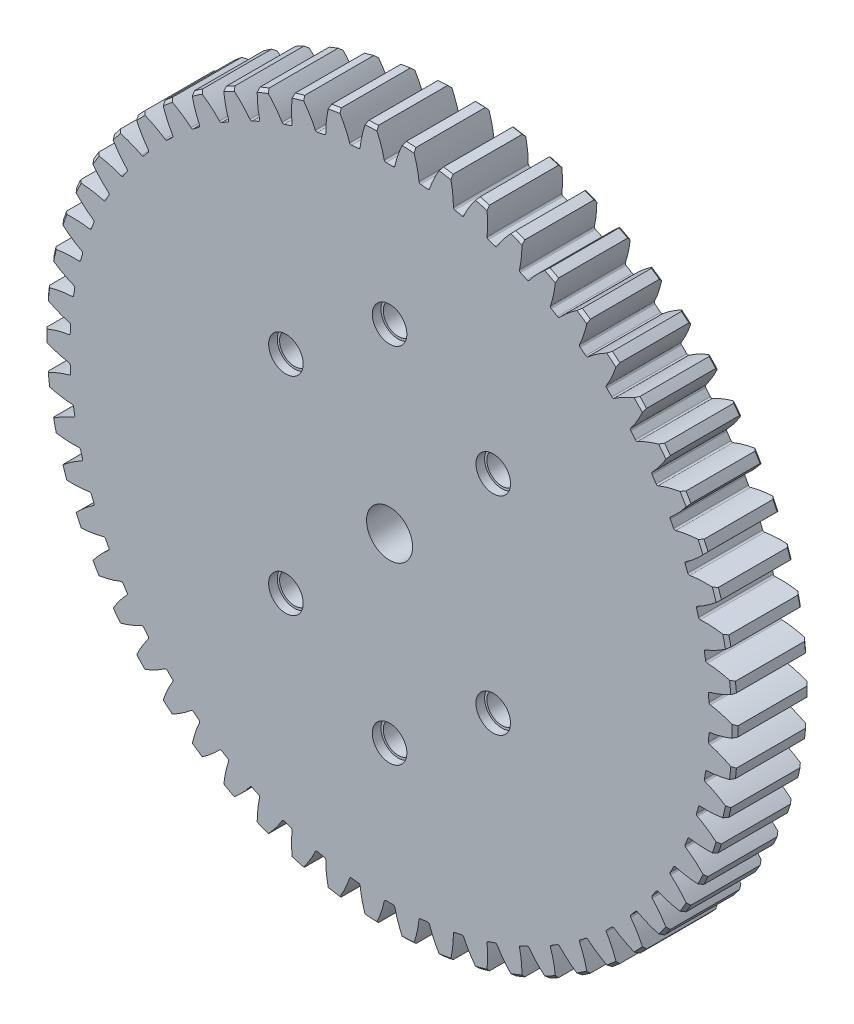
SolidWorks part; units mm, degrees
ref_plane "前视基准面" through (0, 0, 0) normal (0, 0, 1) x (1, 0, 0)
ref_plane "上视基准面" through (0, 0, 0) normal (0, 1, 0) x (1, 0, 0)
ref_plane "右视基准面" through (0, 0, 0) normal (1, 0, 0) x (0, 0, -1)
sketch "直齿轮" plane through (0, 0, 0) normal (0, 0, 1) x (1, 0, 0)
  line L0 (0, 60) -> (0, -60) construction
  line L1 (0, 0) -> (-0.7595, 54.4969)
  line L2 (0, 0) -> (0.7595, 54.4969)
  circle A0 centre (0, 0) radius 60
  arc A1 (1.5706, 57.9787) -> (-1.5706, 57.9787) centre (0, 0) ccw
  circle A2 centre (0, 0) radius 55.5
  circle A3 centre (0, 0) radius 54.5022
  spline S0 degree 4 poles (-0.9179, 54.5383) (-0.9187, 54.5901) (-0.9225, 54.6936) (-0.939, 54.9003) (-0.9775, 55.2089) (-1.0369, 55.5668) (-1.1373, 56.0545) (-1.2779, 56.6187) (-1.4659, 57.2565) (-1.7079, 57.9646) (-2.0987, 58.98) (-2.5766, 60.0423) (-3.1435, 61.1463) (-3.8445, 62.3591) (-4.4961, 63.3921) (-5.4321, 64.7538) (-7.1814, 67.0279) (-10.3067, 70.4206) (-15.1836, 74.5072) (-21.782, 78.5826) (-29.4287, 81.9501) (-37.4287, 84.3454) (-45.6452, 85.8218) (-54.3804, 86.461) (-65.2216, 86.1209) (-78.0109, 84.0601) (-92.368, 79.5208) (-105.4724, 73.0056) (-115.9344, 66.1266) (-125.7118, 58.3273) (-133.2568, 51.1228) (-140.1588, 43.3029) (-146.3909, 34.9507) (-150.9659, 27.9816) (-156.1632, 18.9498) (-160.2078, 10.4812) (-163.3054, 2.739) (-165.6424, -4.1674) (-166.8711, -8.1485) (-167.9932, -12.1608) (-169.009, -16.2015) (-169.9187, -20.267) (-170.7226, -24.3554) (-171.4212, -28.462) (-171.9405, -32.0715) (-172.3204, -35.1711) (-172.5937, -37.7633) (-172.7863, -39.8318) (-172.9532, -41.9187) (-173.094, -43.978) (-173.1994, -45.9041) (-173.275, -47.5621) (-173.3297, -49.1708) (-173.3645, -50.3566) (-173.391, -51.8199) (-173.4021, -52.6794) (-173.4112, -53.9605) (-173.4111, -55.6027) (-173.3855, -57.9403) (-173.3162, -60.4428) (-173.2066, -62.9722) (-173.0882, -65.0648) (-172.9775, -66.7453) (-172.8507, -68.4195) (-172.7079, -70.0956) (-172.5095, -72.1868) (-172.2846, -74.2765) (-172.0335, -76.3624) (-171.8117, -78.029) (-171.6956, -78.8613) (-171.6362, -79.2773) knots 0 0 0 0 0 0.000701 0.001401 0.002802 0.004203 0.005604 0.008133 0.010661 0.01319 0.015718 0.022839 0.026399 0.02996 0.034653 0.039347 0.048734 0.068727 0.096889 0.125051 0.153212 0.181374 0.209535 0.237696 0.271429 0.327752 0.384075 0.440398 0.46856 0.496721 0.553044 0.581206 0.609367 0.637529 0.66569 0.722013 0.736094 0.750174 0.764255 0.778336 0.792417 0.806497 0.820578 0.834659 0.84874 0.85578 0.86282 0.869861 0.876901 0.883942 0.890982 0.895509 0.900036 0.904564 0.909091 0.911932 0.914773 0.920455 0.931818 0.943182 0.948864 0.954545 0.960227 0.965909 0.971591 0.977273 0.988636 0.994318 1 1 1 1 1 construction
  spline S1 degree 4 poles (-0.7595, 54.4969) (-0.7603, 54.5487) (-0.764, 54.6523) (-0.7804, 54.8591) (-0.8187, 55.1679) (-0.8779, 55.526) (-0.9781, 56.0141) (-1.1185, 56.5787) (-1.3063, 57.217) (-1.548, 57.9256) (-1.9384, 58.9418) (-2.4159, 60.005) (-2.9825, 61.11) (-3.6832, 62.3238) (-4.3345, 63.3577) (-5.2702, 64.7208) (-7.0192, 66.9971) (-10.1442, 70.3935) (-15.0215, 74.4853) (-21.6211, 78.5668) (-29.2701, 81.9406) (-37.2732, 84.342) (-45.4934, 85.824) (-54.2331, 86.4687) (-65.0805, 86.1347) (-77.8781, 84.0802) (-92.2459, 79.5468) (-105.3614, 73.0356) (-115.8332, 66.1589) (-125.6206, 58.3609) (-133.174, 51.1569) (-140.0845, 43.3366) (-146.3249, 34.9834) (-150.9065, 28.0132) (-156.112, 18.9794) (-160.1638, 10.5084) (-163.2677, 2.7637) (-165.6099, -4.1452) (-166.8417, -8.1278) (-167.9668, -12.1416) (-168.9855, -16.184) (-169.8981, -20.2513) (-170.7048, -24.3414) (-171.4061, -28.45) (-171.9279, -32.0611) (-172.3099, -35.1622) (-172.5848, -37.7557) (-172.7787, -39.8252) (-172.9469, -41.9132) (-173.089, -43.9735) (-173.1956, -45.9007) (-173.2722, -47.5596) (-173.3278, -49.1691) (-173.3618, -50.3044) (-173.3834, -51.428) (-173.3926, -52.0027) (-173.396, -52.2556) knots 0 0 0 0 0 0.000701 0.001401 0.002802 0.004203 0.005604 0.008133 0.010661 0.01319 0.015718 0.022839 0.026399 0.02996 0.034653 0.039347 0.048734 0.068727 0.096889 0.125051 0.153212 0.181374 0.209535 0.237696 0.271429 0.327752 0.384075 0.440398 0.46856 0.496721 0.553044 0.581206 0.609367 0.637529 0.66569 0.722013 0.736094 0.750174 0.764255 0.778336 0.792417 0.806497 0.820578 0.834659 0.84874 0.85578 0.86282 0.869861 0.876901 0.883942 0.890982 0.895509 0.900036 0.904564 0.908309 0.908309 0.908309 0.908309 0.908309
  spline S2 degree 4 poles (0.9179, 54.5383) (0.9187, 54.5901) (0.9225, 54.6936) (0.939, 54.9003) (0.9775, 55.2089) (1.0369, 55.5668) (1.1373, 56.0545) (1.2779, 56.6187) (1.4659, 57.2565) (1.7079, 57.9646) (2.0987, 58.98) (2.5766, 60.0423) (3.1435, 61.1463) (3.8445, 62.3591) (4.4961, 63.3921) (5.4321, 64.7538) (7.1814, 67.0279) (10.3067, 70.4206) (15.1836, 74.5072) (21.782, 78.5826) (29.4287, 81.9501) (37.4287, 84.3454) (45.6452, 85.8218) (54.3804, 86.461) (65.2216, 86.1209) (78.0109, 84.0601) (92.368, 79.5208) (105.4724, 73.0056) (115.9344, 66.1266) (125.7118, 58.3273) (133.2568, 51.1228) (140.1588, 43.3029) (146.3909, 34.9507) (150.9659, 27.9816) (156.1632, 18.9498) (160.2078, 10.4812) (163.3054, 2.739) (165.6424, -4.1674) (166.8711, -8.1485) (167.9932, -12.1608) (169.009, -16.2015) (169.9187, -20.267) (170.7226, -24.3554) (171.4212, -28.462) (171.9405, -32.0715) (172.3204, -35.1711) (172.5937, -37.7633) (172.7863, -39.8318) (172.9532, -41.9187) (173.094, -43.978) (173.1994, -45.9041) (173.275, -47.5621) (173.3297, -49.1708) (173.3645, -50.3566) (173.391, -51.8199) (173.4021, -52.6794) (173.4112, -53.9605) (173.4111, -55.6027) (173.3855, -57.9403) (173.3162, -60.4428) (173.2066, -62.9722) (173.0882, -65.0648) (172.9775, -66.7453) (172.8507, -68.4195) (172.7079, -70.0956) (172.5095, -72.1868) (172.2846, -74.2765) (172.0335, -76.3624) (171.8117, -78.029) (171.6956, -78.8613) (171.6362, -79.2773) knots 0 0 0 0 0 0.000701 0.001401 0.002802 0.004203 0.005604 0.008133 0.010661 0.01319 0.015718 0.022839 0.026399 0.02996 0.034653 0.039347 0.048734 0.068727 0.096889 0.125051 0.153212 0.181374 0.209535 0.237696 0.271429 0.327752 0.384075 0.440398 0.46856 0.496721 0.553044 0.581206 0.609367 0.637529 0.66569 0.722013 0.736094 0.750174 0.764255 0.778336 0.792417 0.806497 0.820578 0.834659 0.84874 0.85578 0.86282 0.869861 0.876901 0.883942 0.890982 0.895509 0.900036 0.904564 0.909091 0.911932 0.914773 0.920455 0.931818 0.943182 0.948864 0.954545 0.960227 0.965909 0.971591 0.977273 0.988636 0.994318 1 1 1 1 1 construction
  spline S3 degree 4 poles (0.7595, 54.4969) (0.7603, 54.5487) (0.764, 54.6523) (0.7804, 54.8591) (0.8187, 55.1679) (0.8779, 55.526) (0.9781, 56.0141) (1.1185, 56.5787) (1.3063, 57.217) (1.548, 57.9256) (1.9384, 58.9418) (2.4159, 60.005) (2.9825, 61.11) (3.6832, 62.3238) (4.3345, 63.3577) (5.2702, 64.7208) (7.0192, 66.9971) (10.1442, 70.3935) (15.0215, 74.4853) (21.6211, 78.5668) (29.2701, 81.9406) (37.2732, 84.342) (45.4934, 85.824) (54.2331, 86.4687) (65.0805, 86.1347) (77.8781, 84.0802) (92.2459, 79.5468) (105.3614, 73.0356) (115.8332, 66.1589) (125.6206, 58.3609) (133.174, 51.1569) (140.0845, 43.3366) (146.3249, 34.9834) (150.9065, 28.0132) (156.112, 18.9794) (160.1638, 10.5084) (163.2677, 2.7637) (165.6099, -4.1452) (166.8417, -8.1278) (167.9668, -12.1416) (168.9855, -16.184) (169.8981, -20.2513) (170.7048, -24.3414) (171.4061, -28.45) (171.9279, -32.0611) (172.3099, -35.1622) (172.5848, -37.7557) (172.7787, -39.8252) (172.9469, -41.9132) (173.089, -43.9735) (173.1956, -45.9007) (173.2722, -47.5596) (173.3278, -49.1691) (173.3618, -50.3044) (173.3834, -51.428) (173.3926, -52.0027) (173.396, -52.2556) knots 0 0 0 0 0 0.000701 0.001401 0.002802 0.004203 0.005604 0.008133 0.010661 0.01319 0.015718 0.022839 0.026399 0.02996 0.034653 0.039347 0.048734 0.068727 0.096889 0.125051 0.153212 0.181374 0.209535 0.237696 0.271429 0.327752 0.384075 0.440398 0.46856 0.496721 0.553044 0.581206 0.609367 0.637529 0.66569 0.722013 0.736094 0.750174 0.764255 0.778336 0.792417 0.806497 0.820578 0.834659 0.84874 0.85578 0.86282 0.869861 0.876901 0.883942 0.890982 0.895509 0.900036 0.904564 0.908309 0.908309 0.908309 0.908309 0.908309
  dimension "齿顶圆" = 120
  dimension "分度圆" = 116
  dimension "齿根圆" = 111
  dimension "基圆直径" = 109.0043
  dimension "D1" = 3.1416
extrude "齿轮毛坯" add sketch "直齿轮" along normal mid plane 13 contours A0
chamfer "轮齿倒角" distance 0.5 angle 45 2 edges at (60, 0, -6.5) (60, 0, 6.5)
sketch "草图2" plane through (0, 0, 0) normal (0, 0, 1) x (1, 0, 0)
  line L0 (0, 0) -> (-0.7595, 54.4969) construction
  line L1 (0, 0) -> (0.7595, 54.4969) construction
  line L2 (0, 0) -> (-0.7595, 54.4969)
  line L3 (0, 0) -> (0.7595, 54.4969)
  circle A0 centre (0, 0) radius 60 construction
  circle A1 centre (0, 0) radius 60
  circle A2 centre (0, 0) radius 55.5 construction
  circle A3 centre (0, 0) radius 55.5
  spline S0 degree 4 poles (998.4423, 32.7635) (-28.6861, 47.8423) (-1.4617, 50.0963) (-0.5059, 52.6455) (-0.8187, 55.1679) (-0.8779, 55.526) (-0.9781, 56.0141) (-1.1185, 56.5787) (-1.3063, 57.217) (-1.548, 57.9256) (-1.9384, 58.9418) (-2.4159, 60.005) (-2.9825, 61.11) (-3.6832, 62.3238) (-4.3345, 63.3577) (-5.2702, 64.7208) (-7.0192, 66.9971) (-10.1442, 70.3935) (-15.0215, 74.4853) (-21.6211, 78.5668) (-29.2701, 81.9406) (-37.2732, 84.342) (-45.4934, 85.824) (-54.2331, 86.4687) (-65.0805, 86.1347) (-77.8781, 84.0802) (-92.2459, 79.5468) (-105.3614, 73.0356) (-115.8332, 66.1589) (-125.6206, 58.3609) (-133.174, 51.1569) (-140.0845, 43.3366) (-146.3249, 34.9834) (-150.9065, 28.0132) (-156.112, 18.9794) (-160.1638, 10.5084) (-163.2677, 2.7637) (-165.6099, -4.1452) (-166.8417, -8.1278) (-167.9668, -12.1416) (-168.9855, -16.184) (-169.8981, -20.2513) (-170.7048, -24.3414) (-171.4061, -28.45) (-171.9279, -32.0611) (-172.3099, -35.1622) (-172.5848, -37.7557) (-172.7787, -39.8252) (-172.9469, -41.9132) (-173.089, -43.9735) (-173.1956, -45.9007) (-173.2722, -47.5596) (-173.3278, -49.1691) (-173.4461, -53.1212) (-173.4886, -62.192) (-172.6854, -10.7016) (-185.1617, -1051.7117) knots -0.030131 -0.030131 -0.030131 -0.030131 -0.030131 0.000701 0.001401 0.002802 0.004203 0.005604 0.008133 0.010661 0.01319 0.015718 0.022839 0.026399 0.02996 0.034653 0.039347 0.048734 0.068727 0.096889 0.125051 0.153212 0.181374 0.209535 0.237696 0.271429 0.327752 0.384075 0.440398 0.46856 0.496721 0.553044 0.581206 0.609367 0.637529 0.66569 0.722013 0.736094 0.750174 0.764255 0.778336 0.792417 0.806497 0.820578 0.834659 0.84874 0.85578 0.86282 0.869861 0.876901 0.883942 0.890982 0.895509 0.900036 0.904564 0.951302 0.951302 0.951302 0.951302 0.951302 only from (-0.7595, 54.4969) to (-173.396, -52.2556) construction
  spline S1 degree 4 poles (-0.7595, 54.4969) (-0.7603, 54.5487) (-0.764, 54.6523) (-0.7804, 54.8591) (-0.8187, 55.1679) (-0.8779, 55.526) (-0.9781, 56.0141) (-1.1185, 56.5787) (-1.3063, 57.217) (-1.548, 57.9256) (-1.9384, 58.9418) (-2.4159, 60.005) (-2.9825, 61.11) (-3.6832, 62.3238) (-4.3345, 63.3577) (-5.2702, 64.7208) (-7.0192, 66.9971) (-10.1442, 70.3935) (-15.0215, 74.4853) (-21.6211, 78.5668) (-29.2701, 81.9406) (-37.2732, 84.342) (-45.4934, 85.824) (-54.2331, 86.4687) (-65.0805, 86.1347) (-77.8781, 84.0802) (-92.2459, 79.5468) (-105.3614, 73.0356) (-115.8332, 66.1589) (-125.6206, 58.3609) (-133.174, 51.1569) (-140.0845, 43.3366) (-146.3249, 34.9834) (-150.9065, 28.0132) (-156.112, 18.9794) (-160.1638, 10.5084) (-163.2677, 2.7637) (-165.6099, -4.1452) (-166.8417, -8.1278) (-167.9668, -12.1416) (-168.9855, -16.184) (-169.8981, -20.2513) (-170.7048, -24.3414) (-171.4061, -28.45) (-171.9279, -32.0611) (-172.3099, -35.1622) (-172.5848, -37.7557) (-172.7787, -39.8252) (-172.9469, -41.9132) (-173.089, -43.9735) (-173.1956, -45.9007) (-173.2722, -47.5596) (-173.3278, -49.1691) (-173.3618, -50.3044) (-173.3834, -51.428) (-173.3926, -52.0027) (-173.396, -52.2556) knots 0 0 0 0 0 0.000701 0.001401 0.002802 0.004203 0.005604 0.008133 0.010661 0.01319 0.015718 0.022839 0.026399 0.02996 0.034653 0.039347 0.048734 0.068727 0.096889 0.125051 0.153212 0.181374 0.209535 0.237696 0.271429 0.327752 0.384075 0.440398 0.46856 0.496721 0.553044 0.581206 0.609367 0.637529 0.66569 0.722013 0.736094 0.750174 0.764255 0.778336 0.792417 0.806497 0.820578 0.834659 0.84874 0.85578 0.86282 0.869861 0.876901 0.883942 0.890982 0.895509 0.900036 0.904564 0.908309 0.908309 0.908309 0.908309 0.908309
  spline S2 degree 4 poles (-998.4423, 32.7635) (28.6861, 47.8423) (1.4617, 50.0963) (0.5059, 52.6455) (0.8187, 55.1679) (0.8779, 55.526) (0.9781, 56.0141) (1.1185, 56.5787) (1.3063, 57.217) (1.548, 57.9256) (1.9384, 58.9418) (2.4159, 60.005) (2.9825, 61.11) (3.6832, 62.3238) (4.3345, 63.3577) (5.2702, 64.7208) (7.0192, 66.9971) (10.1442, 70.3935) (15.0215, 74.4853) (21.6211, 78.5668) (29.2701, 81.9406) (37.2732, 84.342) (45.4934, 85.824) (54.2331, 86.4687) (65.0805, 86.1347) (77.8781, 84.0802) (92.2459, 79.5468) (105.3614, 73.0356) (115.8332, 66.1589) (125.6206, 58.3609) (133.174, 51.1569) (140.0845, 43.3366) (146.3249, 34.9834) (150.9065, 28.0132) (156.112, 18.9794) (160.1638, 10.5084) (163.2677, 2.7637) (165.6099, -4.1452) (166.8417, -8.1278) (167.9668, -12.1416) (168.9855, -16.184) (169.8981, -20.2513) (170.7048, -24.3414) (171.4061, -28.45) (171.9279, -32.0611) (172.3099, -35.1622) (172.5848, -37.7557) (172.7787, -39.8252) (172.9469, -41.9132) (173.089, -43.9735) (173.1956, -45.9007) (173.2722, -47.5596) (173.3278, -49.1691) (173.4461, -53.1212) (173.4886, -62.192) (172.6854, -10.7016) (185.1617, -1051.7117) knots -0.030131 -0.030131 -0.030131 -0.030131 -0.030131 0.000701 0.001401 0.002802 0.004203 0.005604 0.008133 0.010661 0.01319 0.015718 0.022839 0.026399 0.02996 0.034653 0.039347 0.048734 0.068727 0.096889 0.125051 0.153212 0.181374 0.209535 0.237696 0.271429 0.327752 0.384075 0.440398 0.46856 0.496721 0.553044 0.581206 0.609367 0.637529 0.66569 0.722013 0.736094 0.750174 0.764255 0.778336 0.792417 0.806497 0.820578 0.834659 0.84874 0.85578 0.86282 0.869861 0.876901 0.883942 0.890982 0.895509 0.900036 0.904564 0.951302 0.951302 0.951302 0.951302 0.951302 only from (0.7595, 54.4969) to (173.396, -52.2556) construction
  spline S3 degree 4 poles (0.7595, 54.4969) (0.7603, 54.5487) (0.764, 54.6523) (0.7804, 54.8591) (0.8187, 55.1679) (0.8779, 55.526) (0.9781, 56.0141) (1.1185, 56.5787) (1.3063, 57.217) (1.548, 57.9256) (1.9384, 58.9418) (2.4159, 60.005) (2.9825, 61.11) (3.6832, 62.3238) (4.3345, 63.3577) (5.2702, 64.7208) (7.0192, 66.9971) (10.1442, 70.3935) (15.0215, 74.4853) (21.6211, 78.5668) (29.2701, 81.9406) (37.2732, 84.342) (45.4934, 85.824) (54.2331, 86.4687) (65.0805, 86.1347) (77.8781, 84.0802) (92.2459, 79.5468) (105.3614, 73.0356) (115.8332, 66.1589) (125.6206, 58.3609) (133.174, 51.1569) (140.0845, 43.3366) (146.3249, 34.9834) (150.9065, 28.0132) (156.112, 18.9794) (160.1638, 10.5084) (163.2677, 2.7637) (165.6099, -4.1452) (166.8417, -8.1278) (167.9668, -12.1416) (168.9855, -16.184) (169.8981, -20.2513) (170.7048, -24.3414) (171.4061, -28.45) (171.9279, -32.0611) (172.3099, -35.1622) (172.5848, -37.7557) (172.7787, -39.8252) (172.9469, -41.9132) (173.089, -43.9735) (173.1956, -45.9007) (173.2722, -47.5596) (173.3278, -49.1691) (173.3618, -50.3044) (173.3834, -51.428) (173.3926, -52.0027) (173.396, -52.2556) knots 0 0 0 0 0 0.000701 0.001401 0.002802 0.004203 0.005604 0.008133 0.010661 0.01319 0.015718 0.022839 0.026399 0.02996 0.034653 0.039347 0.048734 0.068727 0.096889 0.125051 0.153212 0.181374 0.209535 0.237696 0.271429 0.327752 0.384075 0.440398 0.46856 0.496721 0.553044 0.581206 0.609367 0.637529 0.66569 0.722013 0.736094 0.750174 0.764255 0.778336 0.792417 0.806497 0.820578 0.834659 0.84874 0.85578 0.86282 0.869861 0.876901 0.883942 0.890982 0.895509 0.900036 0.904564 0.908309 0.908309 0.908309 0.908309 0.908309
extrude "插齿" cut sketch "草图2" against normal mid plane 13 contours A3 S3 A1 S1 region at (0, 58.1189, 0)
fillet "圆角1" [suppressed] radius 0.3
pattern_circular "圆周阵列1" [suppressed] count 58 over 360 of bodies 102
fillet "圆角2" radius 0.3 2 edges at (0.8753, 55.4931, 0) (-0.8753, 55.4931, 0)
pattern_circular "圆周阵列2" count 58 over 360 about axis through (0, 0, 6.5) along (0, 0, -1) of "插齿", "圆角2"
pattern_circular "圆周阵列3" [suppressed] count 58 over 360 of bodies 102
sketch "分度圆" plane through (0, 0, 0) normal (0, 0, 1) x (1, 0, 0)
  circle A0 centre (0, 0) radius 58 construction
sketch "草图3" plane through (0, 0, -6.5) normal (0, 0, -1) x (-1, 0, 0)
  circle A0 centre (0, 31.5) radius 3
  circle A1 centre (0, -31.5) radius 3
  circle A96 centre (0, 0) radius 31.5 construction
  dimension "D1" = 63
  dimension "D2" = 6
  dimension "D3" = 6
sketch "草图7" plane through (0, 0, -6.5) normal (0, 0, -1) x (-1, 0, 0)
  circle A0 centre (0, 0) radius 4
  dimension "D1" = 8
extrude "切除-拉伸1" cut sketch "草图7" against normal blind 20
sketch "草图9" plane through (0, 0, -6.5) normal (0, 0, -1) x (-1, 0, 0)
  line L1 (-18, 18) -> (18, 18)
  line L2 (-18, 18) -> (-18, -18)
  line L3 (-18, -18) -> (18, -18)
  line L4 (18, 18) -> (18, -18)
  circle A0 centre (18, 18) radius 3
  circle A1 centre (-18, 18) radius 3
  circle A2 centre (18, -18) radius 3
  circle A3 centre (-18, -18) radius 3
  point P0 (-18, 18)
  point P1 (18, -18)
  point P2 (-18, -18)
  point P3 (18, 18)
  point P4 (18, 0)
  point P5 (0, 18)
  dimension "D3" = 6
  dimension "D4" = 6
  dimension "D5" = 6
  dimension "D6" = 6
  dimension "D1" = 36
  dimension "D2" = 36
sketch "草图12" plane through (0, 0, -6.5) normal (0, 0, -1) x (-1, 0, 0)
  circle A0 centre (0, 0) radius 36
  dimension "D1" = 72
extrude "凸台-拉伸1" add sketch "草图12" along normal blind 7.1 from surface starting at face at (-4, 0, -6.5)
extrude "切除-拉伸2" cut sketch "草图9" along normal blind 1.5 from surface contours L1 A1 L2 | L2 A1 L1 | L1 A0 L4 | L4 A0 L1 | L3 A2 L4 | L4 A2 L3 | L2 A3 L3 | L3 A3 L2 region at (18.4244, 18.4244, -6.5) region at (16.7268, 16.7268, -6.5) region at (-18.4244, 18.4244, -6.5) region at (-16.7268, 16.7268, -6.5) region at (16.7268, -16.7268, -6.5) region at (18.4244, -18.4244, -6.5) region at (-18.4244, -18.4244, -6.5) region at (-16.7268, -16.7268, -6.5) starting at face at (4, 0, 6.5)
sketch "草图13" plane through (0, 0, 6.5) normal (0, 0, 1) x (1, 0, 0)
  circle A0 centre (-18, 18) radius 2.6
  circle A2 centre (18, 18) radius 2.6
  circle A3 centre (18, -18) radius 2.6
  circle A4 centre (-18, -18) radius 2.6
  dimension "D1" = 5.2
  dimension "D2" = 5.2
  dimension "D3" = 5.2
  dimension "D4" = 5.2
extrude "切除-拉伸3" cut sketch "草图13" against normal blind 8
extrude "切除-拉伸4" cut sketch "草图3" along normal blind 1.5 from surface starting at face at (21, -18, 6.5)
sketch "草图14" plane through (0, 0, 5) normal (0, 0, 1) x (1, 0, 0)
  circle A0 centre (0, -31.5) radius 2.6
  circle A1 centre (0, 31.5) radius 2.6
  dimension "D1" = 5.2
  dimension "D2" = 5.2
extrude "切除-拉伸5" cut sketch "草图14" against normal blind 6
sketch "草图15" plane through (0, 0, -13.6) normal (0, 0, -1) x (-1, 0, 0)
  circle A0 centre (0, 0) radius 30
  circle A1 centre (0, 0) radius 10
  dimension "D1" = 20
  dimension "D2" = 60
extrude "切除-拉伸6" cut sketch "草图15" against normal blind 5
sketch "草图16" plane through (0, 0, -8.6) normal (0, 0, -1) x (-1, 0, 0)
  line L0 (-2, 9.798) -> (-2, 29.9333)
  line L1 (2, 29.9333) -> (2, 9.798)
  circle A0 centre (0, 0) radius 30 construction
  circle A1 centre (0, 0) radius 10
  circle A2 centre (0, 0) radius 10
  circle A3 centre (0, 0) radius 30
  circle A4 centre (0, 0) radius 30
  circle A5 centre (0, 0) radius 10 construction
  circle M5 centre (0, 0) radius 10
  circle M6 centre (0, 0) radius 30
  dimension "D3" = 4
  dimension "D4" = 2
  dimension "D1" = 0
  dimension "D2" = 0
extrude "凸台-拉伸2" add sketch "草图16" along normal up to surface (5 mm away) contours L1 L0 M6 M5 region at (0, 19.9553, -8.6) up to face at (-10, 0, -13.6)
pattern_circular "阵列(圆周)1" count 6 every 60 about axis through (0, 0, -13.6) along (0, 0, 1) of "凸台-拉伸2"
fillet "圆角3" radius 1 24 edges at (-5, 8.6603, -8.6) (-2, 19.8656, -8.6) (-15, 25.9808, -8.6) (-16.2041, 11.6649, -8.6) (15, 25.9808, -8.6) (2, 19.8656, -8.6) (5, 8.6603, -8.6) (16.2041, 11.6649, -8.6) (10, 0, -8.6) (18.2041, -8.2008, -8.6) (30, 0, -8.6) (18.2041, 8.2008, -8.6) (-10, 0, -8.6) (-18.2041, 8.2008, -8.6) (-30, 0, -8.6) (-18.2041, -8.2008, -8.6) (-5, -8.6603, -8.6) (-16.2041, -11.6649, -8.6) (-15, -25.9808, -8.6) (-2, -19.8656, -8.6) (5, -8.6603, -8.6) (2, -19.8656, -8.6) (15, -25.9808, -8.6) (16.2041, -11.6649, -8.6)
equation "\"m\"= 2'模数"
equation "\"z\"= 58'齿数"
equation "\"a\"= 20'压力角（常见为20°）"
equation "\"B\"= 13'齿宽"
equation "\"C1\"= 0.5'轮齿倒角（若设为0，则无倒角）"
equation "\"R\"= 0.3'齿根圆角（若设为0，则无圆角）"
equation "\"x\"= 0'变位系数"
equation "\"ha\"= 1'齿顶高系数"
equation "\"c\"= 0.25'顶隙系数"
equation "\"分度圆@直齿轮\"=\"m\" * \"z\""
equation "\"齿顶圆@直齿轮\" = \"m\" * ( \"z\" + 2 * ( \"ha\" + \"x\" ) )"
equation "\"齿根圆@直齿轮\" = \"m\" * ( \"z\" - 2 * ( \"ha\" - \"x\" + \"c\" ) )"
equation "\"基圆直径@直齿轮\"= \"m\" * \"z\" * cos ( \"a\" )"
equation "\"D1@直齿轮\"= \"m\" * ( pi / 2 ) - 2 * \"m\" * tan ( \"a\" ) * \"x\"'作者：机械菌-"
equation "\"圆周阵列3\"= IIF ( \"R\">0 , \"suppressed\" , \"unsuppressed\" )"
equation "\"圆角1\"=IIF ( \"R\">0 ,IIF ( \"m\" * ( \"z\" - 2 * ( \"ha\" - \"x\" + \"c\" ) ) < \"m\" * \"z\" * cos ( \"a\" ) , \"unsuppressed\" , \"suppressed\" ) , \"suppressed\" )"
equation "\"圆周阵列1\"=IIF ( \"R\">0 , IIF ( \"m\" * ( \"z\" - 2 * ( \"ha\" - \"x\" + \"c\" ) ) < \"m\" * \"z\" * cos ( \"a\" ) , \"unsuppressed\" , \"suppressed\" ), \"suppressed\" )"
equation "\"圆角2\"=IIF ( \"R\">0 ,IIF ( \"m\" * ( \"z\" - 2 * ( \"ha\" - \"x\" + \"c\" ) ) > \"m\" * \"z\" * cos ( \"a\" ) , \"unsuppressed\" , \"suppressed\" ) , \"suppressed\" )"
equation "\"圆周阵列2\"=IIF ( \"R\">0 , IIF ( \"m\" * ( \"z\" - 2 * ( \"ha\" - \"x\" + \"c\" ) ) > \"m\" * \"z\" * cos ( \"a\" ) , \"unsuppressed\" , \"suppressed\" ), \"suppressed\" )"
equation "\"轮齿倒角\"= IIF ( \"C1\" > 0 , \"unsuppressed\" , \"suppressed\" )"
